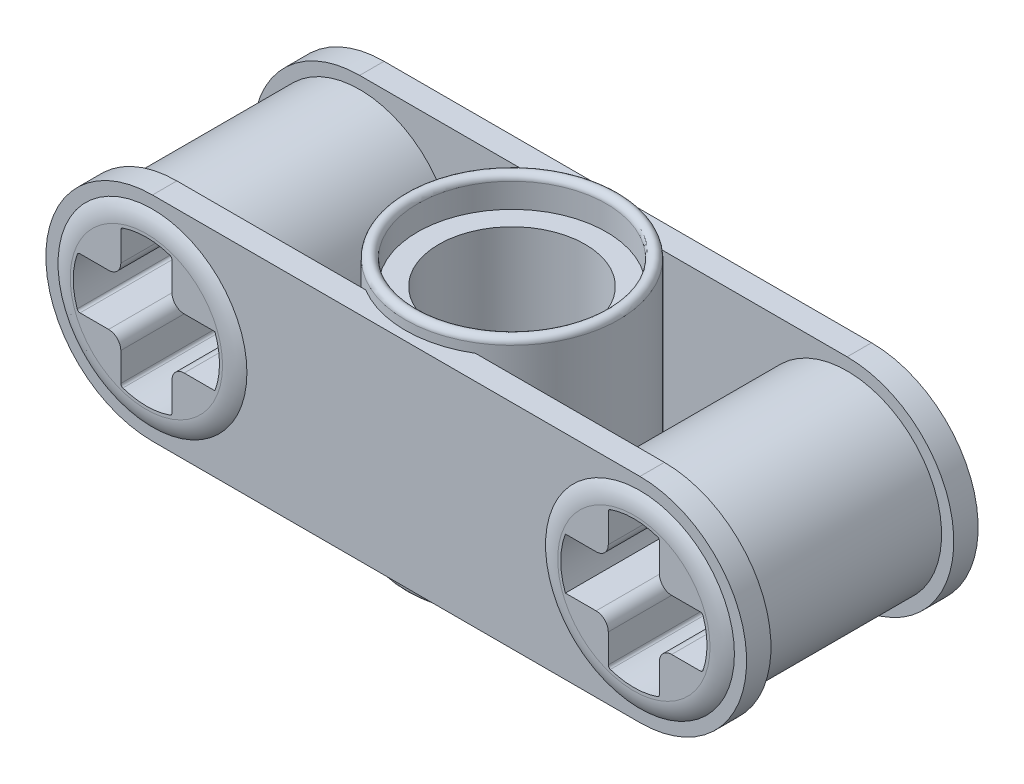
SolidWorks part; units mm, degrees
ref_plane "Front Plane" through (0, 0, 0) normal (0, 0, 1) x (1, 0, 0)
ref_plane "Top Plane" through (0, 0, 0) normal (0, 1, 0) x (1, 0, 0)
ref_plane "Right Plane" through (0, 0, 0) normal (1, 0, 0) x (0, 0, -1)
sketch "Sketch1" plane through (0, 0, 0) normal (0, 0, 1) x (1, 0, 0)
  line L1 (-9.24, 0.84) -> (-10.1777, 0.84)
  line L2 (-8.84, -2.1777) -> (-8.84, -1.24)
  line L3 (-7.16, -2.1777) -> (-7.16, -1.24)
  line L6 (-8.84, 1.24) -> (-8.84, 2.1777)
  line L7 (-7.16, 1.24) -> (-7.16, 2.1777)
  line L8 (-9.24, -0.84) -> (-10.1777, -0.84)
  line L14 (8.84, 1.24) -> (8.84, 2.1777)
  line L15 (7.16, 1.24) -> (7.16, 2.1777)
  line L22 (7.16, -2.1777) -> (7.16, -1.24)
  line L23 (8.84, -2.1777) -> (8.84, -1.24)
  line L24 (9.24, -0.84) -> (10.1777, -0.84)
  line L25 (9.24, 0.84) -> (10.1777, 0.84)
  line L31 (6.76, -0.84) -> (5.7518, -0.84)
  line L32 (6.76, 0.84) -> (5.7518, 0.84)
  line L33 (-6.76, 0.84) -> (-5.7518, 0.84)
  line L34 (-6.76, -0.84) -> (-5.7518, -0.84)
  arc A9 (-7.2278, 2.2724) -> (-8.7722, 2.2724) centre (-8, 0) ccw
  arc A10 (-10.2724, 0.7722) -> (-10.2724, -0.7722) centre (-8, 0) ccw
  arc A11 (-8.7722, -2.2724) -> (-7.2278, -2.2724) centre (-8, 0) ccw
  arc A12 (-8.84, -1.24) -> (-9.24, -0.84) centre (-9.24, -1.24) ccw
  arc A13 (-7.16, -1.24) -> (-6.76, -0.84) centre (-6.76, -1.24) cw
  arc A14 (-6.76, 0.84) -> (-7.16, 1.24) centre (-6.76, 1.24) cw
  arc A15 (-9.24, 0.84) -> (-8.84, 1.24) centre (-9.24, 1.24) ccw
  arc A16 (-10.1777, 0.84) -> (-10.2724, 0.7722) centre (-10.1777, 0.74) ccw
  arc A17 (-10.1777, -0.84) -> (-10.2724, -0.7722) centre (-10.1777, -0.74) cw
  arc A18 (-8.7722, -2.2724) -> (-8.84, -2.1777) centre (-8.74, -2.1777) cw
  arc A19 (-7.2278, -2.2724) -> (-7.16, -2.1777) centre (-7.26, -2.1777) ccw
  arc A20 (-7.2278, 2.2724) -> (-7.16, 2.1777) centre (-7.26, 2.1777) cw
  arc A21 (-8.84, 2.1777) -> (-8.7722, 2.2724) centre (-8.74, 2.1777) cw
  arc A39 (9.24, 0.84) -> (8.84, 1.24) centre (9.24, 1.24) cw
  arc A40 (8.84, 2.1777) -> (8.7722, 2.2724) centre (8.74, 2.1777) ccw
  arc A41 (7.2278, 2.2724) -> (8.7722, 2.2724) centre (8, 0) cw
  arc A42 (7.2278, 2.2724) -> (7.16, 2.1777) centre (7.26, 2.1777) ccw
  arc A43 (6.76, 0.84) -> (7.16, 1.24) centre (6.76, 1.24) ccw
  arc A45 (7.16, -1.24) -> (6.76, -0.84) centre (6.76, -1.24) ccw
  arc A46 (7.2278, -2.2724) -> (7.16, -2.1777) centre (7.26, -2.1777) cw
  arc A47 (8.7722, -2.2724) -> (7.2278, -2.2724) centre (8, 0) cw
  arc A48 (8.7722, -2.2724) -> (8.84, -2.1777) centre (8.74, -2.1777) ccw
  arc A49 (8.84, -1.24) -> (9.24, -0.84) centre (9.24, -1.24) cw
  arc A50 (10.1777, -0.84) -> (10.2724, -0.7722) centre (10.1777, -0.74) ccw
  arc A51 (10.2724, 0.7722) -> (10.2724, -0.7722) centre (8, 0) cw
  arc A52 (10.1777, 0.84) -> (10.2724, 0.7722) centre (10.1777, 0.74) cw
  circle A60 centre (-8, 0) radius 2.4
  circle A61 centre (8, 0) radius 2.4
  circle A62 centre (-8, 0) radius 3.1
  circle A63 centre (8, 0) radius 3.1
  arc A65 (-5.7518, 0.84) -> (-5.7518, -0.84) centre (-8, 0) cw
  arc A66 (5.7518, 0.84) -> (5.7518, -0.84) centre (8, 0) ccw
  point P115 (0, 3.3)
  point P118 (0, -3.3)
  dimension "D1" = 4.8
  dimension "D4" = 6.2
  dimension "D2" = 4.8
  dimension "D3" = 6.2
extrude "Boss-Extrude1" add sketch "Sketch1" along normal mid plane 8 contours A63 A61 A51 A47 A41 | A52 A61 A40 L14 A39 L25 | A42 A61 L32 A43 L15 | A48 A61 A50 L24 A49 L23 | L31 A61 A46 L22 A45 | L33 A60 A20 L7 A14 | A62 A60 A9 A11 A10 | A19 A60 L34 A13 L3 | A17 A60 A18 L2 A12 L8 | A21 A60 A16 L1 A15 L6 region at (-9.3889, 1.3889, 0) region at (-9.3889, -1.3889, 0) region at (-6.6117, 1.3893, 0) region at (-6.6117, -1.3893, 0) region at (9.3889, 1.3889, 0) region at (6.6117, 1.3893, 0) region at (6.6117, -1.3893, 0) region at (9.3889, -1.3889, 0) region at (-11.0123, 0, 0) region at (4.9877, 0, 0)
ref_plane "Plane1" through (0, 0, 3) normal (0, 0, 1) x (1, 0, 0)
sketch "Sketch2" plane through (0, 0, 3) normal (0, 0, 1) x (1, 0, 0)
  line L0 (-8, 3.5) -> (8, 3.5)
  line L1 (-8, -3.5) -> (8, -3.5)
  arc A2 (-8, 3.5) -> (-8, -3.5) centre (-8, 0) ccw
  arc A3 (8, 3.5) -> (8, -3.5) centre (8, 0) cw
  circle A4 centre (-8, 0) radius 3.1
  circle A5 centre (8, 0) radius 3.1
extrude "Boss-Extrude2" add sketch "Sketch2" along normal blind 0.8
fillet "Fillet2" radius 1 1 edges at (-4.9, 0, 4)
fillet "Fillet3" radius 1 1 edges at (11.1, 0, 4)
mirror "Mirror2" about plane through (0, 0, 0) normal (0, 0, 1) of "Boss-Extrude2"
fillet "Fillet7" radius 1 1 edges at (11.1, 0, -4)
fillet "Fillet8" radius 1 1 edges at (-4.9, 0, -4)
sketch "Sketch4" plane through (0, 0, 0) normal (0, 1, 0) x (1, 0, 0)
  circle A0 centre (0, 0) radius 3.5
  circle A1 centre (0, 0) radius 2.4
  dimension "D1" = 7
  dimension "D2" = 4.8
extrude "Boss-Extrude3" add sketch "Sketch4" along normal mid plane 8
sketch "Sketch6" plane through (0, 4, 0) normal (0, 1, 0) x (1, 0, 0)
  circle A0 centre (0, 0) radius 3.1
  dimension "D1" = 6.2
extrude "Cut-Extrude1" cut sketch "Sketch6" against normal blind 1
mirror "Mirror5" about plane through (0, 0, 0) normal (0, 1, 0) of "Cut-Extrude1"
fillet "Fillet10" 2 edges at (0, 4, 3.1) (0, 4, 3.5) type full round first side face at (0, 3, 3.1) second side face at (0, 4, 3.5) middle face at (0, 4, 3.1)
fillet "Fillet11" 2 edges at (0, -4, 3.1) (0, -4, 3.5) type full round first side face at (0, -3, 3.1) second side face at (0, 3.8, 3.5) middle face at (0, -4, 3.1)
